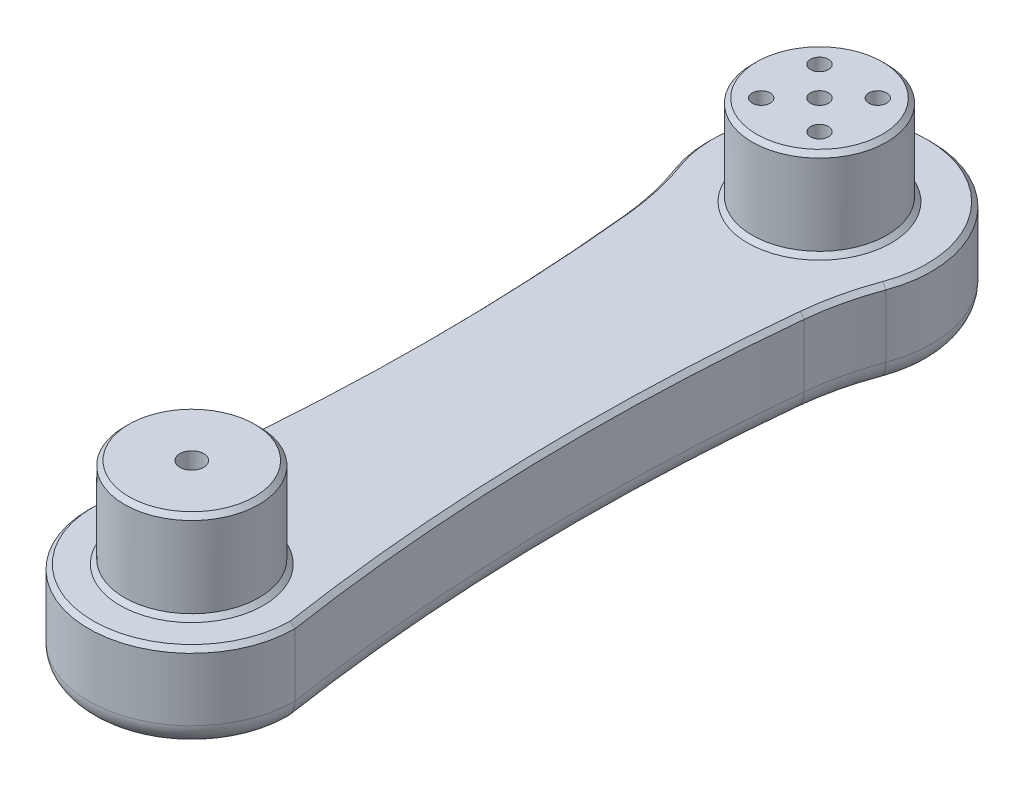
SolidWorks part; units mm, degrees
ref_plane "Front Plane" through (0, 0, 0) normal (0, 0, 1) x (1, 0, 0)
ref_plane "Top Plane" through (0, 0, 0) normal (0, 1, 0) x (1, 0, 0)
ref_plane "Right Plane" through (0, 0, 0) normal (1, 0, 0) x (0, 0, -1)
sketch "Sketch1" plane through (0, 0, 0) normal (0, 1, 0) x (1, 0, 0)
  line L0 (0, 0) -> (0, 140) construction
  line L1 (0, 71.7271) -> (35.776, 71.7271) construction
  arc A6 (-23, 0) -> (23, 0) centre (0, 0) ccw
  arc A11 (20.0339, 116.5546) -> (23, 0) centre (482.1657, 70) ccw
  arc A12 (23.4505, 131.3355) -> (-23.4505, 131.3355) centre (0, 140) ccw
  arc A13 (-20.0339, 116.5546) -> (-23, 0) centre (-482.1657, 70) cw
  arc A14 (20.0339, 116.5546) -> (23.4505, 131.3355) centre (79.7317, 110.5407) cw
  arc A15 (-23.4505, 131.3355) -> (-20.0339, 116.5546) centre (-79.7317, 110.5407) cw
  point P11 (21.1687, 126.7001)
  point P18 (-21.1687, 126.7001)
  dimension "D1" = 60
  dimension "D2" = 140
extrude "Boss-Extrude1" add sketch "Sketch1" along normal blind 20
sketch "Sketch2" plane through (0, 20, 0) normal (0, 1, 0) x (1, 0, 0)
  circle A0 centre (0, 0) radius 15.01
  dimension "D1" = 30.02
extrude "Boss-Extrude2" add sketch "Sketch2" along normal blind 20
chamfer "Chamfer1" distance 1 angle 45 1 edges at (0, 40, 15.01)
sketch "Sketch3" plane through (0, 20, 0) normal (0, 1, 0) x (1, 0, 0)
  circle A1 centre (0, 140) radius 18.485
  dimension "D1" = 36.97
chamfer "Chamfer3" distance 1 angle 45 7 edges at (0, 20, 23) (0, 20, -15.01) (17.8452, 20, -58.1839) (-17.8452, 20, -58.1839) (-21.2732, 20, -124.0535) (0, 20, -165) (21.2732, 20, -124.0535)
sketch "Sketch5" plane through (0, 40, 0) normal (0, 1, 0) x (1, 0, 0)
  circle A0 centre (0, 0) radius 2.65
  dimension "D1" = 5.3
extrude "Cut-Extrude2" cut sketch "Sketch5" against normal blind 40
ref_plane "Plane1" through (0, 10, 0) normal (0, 1, 0) x (1, 0, 0)
fillet "Fillet3" radius 5 6 edges at (-17.8452, 0, -58.1839) (-21.2732, 0, -124.0535) (0, 0, -165) (21.2732, 0, -124.0535) (0, 0, 23) (17.8452, 0, -58.1839)
sketch "Sketch6" plane through (0, 0, 0) normal (0, -1, 0) x (1, 0, 0)
  circle A0 centre (0, 0) radius 3.65
  dimension "D1" = 7.3
extrude "Cut-Extrude3" cut sketch "Sketch6" against normal blind 8
chamfer "Chamfer4" distance 0.5 angle 45 1 edges at (0, 0, -3.65)
sketch "Sketch10" plane through (0, 20, 0) normal (0, 1, 0) x (1, 0, 0)
  circle A0 centre (0, 140) radius 15.01
  dimension "D1" = 30.02
extrude "Boss-Extrude5" add sketch "Sketch10" along normal blind 20
chamfer "Chamfer5" distance 1 angle 45 2 edges at (0, 20, -155.01) (0, 40, -124.99)
sketch "Sketch11" plane through (0, 40, 0) normal (0, 1, 0) x (1, 0, 0)
  circle A0 centre (0, 140) radius 2.01
  dimension "D1" = 4.02
extrude "Cut-Extrude5" cut sketch "Sketch11" against normal blind 40
sketch "Sketch12" plane through (0, 40, 0) normal (0, 1, 0) x (1, 0, 0)
  line L5 (-6.5, 146.5) -> (6.5, 133.5) construction
  line L6 (-6.5, 133.5) -> (6.5, 146.5) construction
  circle A0 centre (-6.5, 146.5) radius 2
  circle A1 centre (-6.5, 133.5) radius 2
  circle A2 centre (6.5, 133.5) radius 2
  circle A3 centre (6.5, 146.5) radius 2
  point P0 (0, 140)
  point P8 (0, 0)
  point P9 (0, 0)
  dimension "D3" = 4
  dimension "D4" = 4
  dimension "D1" = 13
  dimension "D2" = 13
  dimension "D5" = 0
  dimension "D6" = 0
  dimension "D7" = 13
  dimension "D8" = 13
extrude "Cut-Extrude6" cut sketch "Sketch12" against normal blind 20
